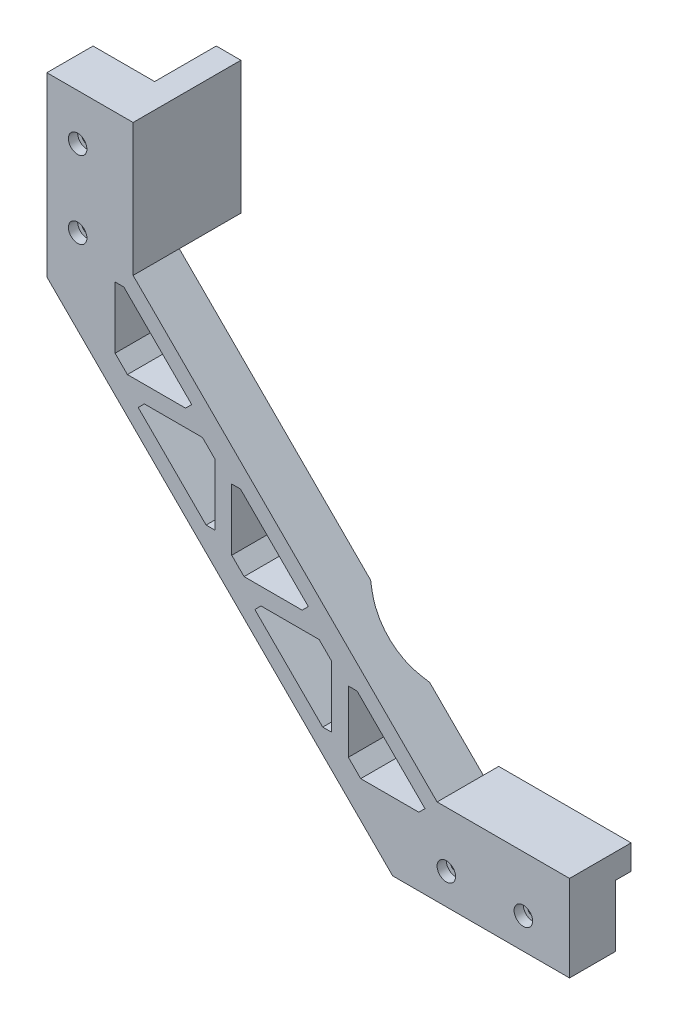
SolidWorks part; units mm, degrees
ref_plane "前视基准面" through (0, 0, 0) normal (0, 0, 1) x (1, 0, 0)
ref_plane "上视基准面" through (0, 0, 0) normal (0, 1, 0) x (1, 0, 0)
ref_plane "右视基准面" through (0, 0, 0) normal (1, 0, 0) x (0, 0, -1)
other "Configuration Table"
sketch "草图1" plane through (0, 0, 0) normal (0, 0, 1) x (1, 0, 0)
  line L0 (124.695, -160) -> (159.695, -160)
  line L1 (172.695, -180) -> (-7.695, -180) construction
  line L2 (159.695, -160) -> (159.695, -180)
  line L3 (159.695, -180) -> (102.2686, -180)
  line L4 (102.2686, -180) -> (-10, -67.7314)
  line L5 (17.8609, -53.1659) -> (-3.3523, -74.3791) construction
  line L6 (-10, -67.7314) -> (-10, -10.305)
  line L7 (-10, -10.305) -> (10, -10.305)
  line L8 (10, -10.305) -> (10, -45.305)
  line L9 (10, -45.305) -> (124.695, -160)
  line L10 (-10, 104.4) -> (-10, -160) construction
  line L11 (10, 104.4) -> (10, -160) construction
  line L12 (-14.695, -160) -> (159.695, -160) construction
  line L14 (159.695, -172.7737) -> (159.695, -167.2263) construction
  dimension "D1" = 35
  dimension "D2" = 35
  dimension "D3" = 30
extrude "凸台-拉伸1" add sketch "草图1" along normal blind 15
sketch "草图3" plane through (0, 0, 15) normal (0, 0, 1) x (1, 0, 0)
  line L0 (159.695, -160) -> (116.695, -160)
  line L2 (124.695, -160) -> (10, -45.305) construction
  line L3 (116.695, -152) -> (159.695, -152)
  line L4 (159.695, -152) -> (159.695, -160)
  line L5 (116.695, -152) -> (116.695, -160)
  dimension "D1" = 8
extrude "凸台-拉伸2" add sketch "草图3" against normal blind 35
sketch "草图4" plane through (0, 0, 15) normal (0, 0, 1) x (1, 0, 0)
  line L0 (10, -45.305) -> (10, -10.305) construction
  line L1 (10, -10.305) -> (18, -10.305)
  line L2 (10, -10.305) -> (10, -53.305)
  line L3 (10, -53.305) -> (18, -53.305)
  line L4 (18, -10.305) -> (18, -53.305)
  line L6 (10, -10.305) -> (-10, -10.305) construction
  line L7 (116.695, -152) -> (10, -45.305) construction
  dimension "D1" = 8
extrude "凸台-拉伸3" add sketch "草图4" against normal blind 35
sketch "草图5" plane through (0, 0, 15) normal (0, 0, 1) x (1, 0, 0)
  line L4 (50.0234, -93.1066) -> (50.0234, -119.9766)
  line L5 (50.0234, -119.9766) -> (76.8934, -119.9766)
  line L6 (76.8934, -119.9766) -> (50.0234, -93.1066)
  line L7 (55.5234, -125.4766) -> (82.3934, -125.4766)
  line L8 (82.3934, -125.4766) -> (82.3934, -152.3467)
  line L9 (82.3934, -152.3467) -> (55.5234, -125.4766)
  line L10 (12.1533, -55.2365) -> (12.1533, -82.1066)
  line L11 (12.1533, -82.1066) -> (39.0234, -82.1066)
  line L12 (39.0234, -82.1066) -> (12.1533, -55.2365)
  line L13 (87.8934, -130.9766) -> (87.8934, -157.8467)
  line L15 (116.695, -152) -> (18, -53.305) construction
  line L16 (17.6533, -87.6066) -> (44.5234, -87.6066)
  line L17 (44.5234, -87.6066) -> (44.5234, -114.4766)
  line L18 (44.5234, -114.4766) -> (17.6533, -87.6066)
  line L19 (-10, -67.7314) -> (102.2686, -180) construction
  line L20 (35.9264, -79.0096) -> (39.7761, -82.8593) construction
  line L21 (15.6753, -85.6286) -> (-21.6148, -48.3384) construction
  line L22 (33.1355, -76.2186) -> (37.0245, -72.3295) construction
  line L23 (19.2968, -89.2501) -> (15.4078, -93.1392) construction
  line L24 (24.3585, -82.1066) -> (24.3585, -87.6066) construction
  line L25 (87.8934, -157.8467) -> (114.7635, -157.8467)
  line L26 (114.7635, -157.8467) -> (87.8934, -130.9766)
  line L27 (44.5234, -103.4947) -> (50.0234, -103.4947) construction
  line L28 (68.5928, -119.9766) -> (68.5928, -125.4766) construction
  line L29 (82.3934, -131.3401) -> (87.8934, -131.3401) construction
  line L30 (12.1533, -76.2143) -> (12.1533, -105.29) construction
  line L31 (10, -98.1526) -> (12.1533, -98.1526) construction
  line L32 (10, 104.4) -> (10, -160) construction
  line L33 (87.8934, -157.8467) -> (71.7553, -157.8467) construction
  line L35 (74.4155, -157.8467) -> (74.4155, -160) construction
  line L36 (-14.695, -160) -> (159.695, -160) construction
  dimension "D1" = 5.5
extrude "切除-拉伸1" cut sketch "草图5" against normal through all
sketch "草图6" plane through (0, 0, 15) normal (0, 0, 1) x (1, 0, 0)
  line L0 (2.7737, 104.4) -> (-2.7737, 104.4) construction
  line L1 (173.595, -172.7737) -> (173.595, -167.2263) construction
  line L2 (159.695, -180) -> (159.695, -152) construction
  line L3 (18, -10.305) -> (-10, -10.305) construction
  circle A0 centre (0, -50.305) radius 1.6
  circle A1 centre (0, -25.305) radius 1.6
  circle A2 centre (119.695, -170) radius 1.6
  circle A3 centre (144.695, -170) radius 1.6
  point P10 (0, 104.4)
  point P13 (173.595, -170)
  dimension "D1" = 3.2
  dimension "D2" = 15
  dimension "D3" = 25
  dimension "D4" = 15
  dimension "D5" = 25
extrude "切除-拉伸2" cut sketch "草图6" against normal through all
sketch "草图7" plane through (0, 0, 15) normal (0, 0, 1) x (1, 0, 0)
  circle A0 centre (0, -25.305) radius 3
  circle A1 centre (144.695, -170) radius 1.6
  circle A2 centre (144.695, -170) radius 1.6 construction
  circle A3 centre (119.695, -170) radius 1.6
  circle A4 centre (119.695, -170) radius 1.6 construction
  circle A5 centre (0, -25.305) radius 1.6
  circle A6 centre (0, -25.305) radius 1.6 construction
  circle A7 centre (0, -50.305) radius 1.6
  circle A8 centre (0, -50.305) radius 1.6 construction
  circle A9 centre (0, -50.305) radius 3
  circle A10 centre (119.695, -170) radius 3
  circle A11 centre (144.695, -170) radius 3
  dimension "D5" = 6
  dimension "D1" = 0
  dimension "D2" = 0
  dimension "D3" = 0
  dimension "D4" = 0
extrude "切除-拉伸3" cut sketch "草图7" against normal blind 3
chamfer "倒角1" distance 4 angle 45 15 edges at (55.5234, -125.4766, 7.5) (82.3934, -125.4766, 7.5) (87.8934, -130.9766, 7.5) (76.8934, -119.9766, 7.5) (50.0234, -119.9766, 7.5) (87.8934, -157.8467, 7.5) (114.7635, -157.8467, 7.5) (82.3934, -152.3467, 7.5) (44.5234, -114.4766, 7.5) (17.6533, -87.6066, 7.5) (44.5234, -87.6066, 7.5) (39.0234, -82.1066, 7.5) (12.1533, -82.1066, 7.5) (12.1533, -55.2365, 7.5) (50.0234, -93.1066, 7.5)
sketch "草图8" plane through (159.695, 0, 0) normal (1, 0, 0) x (0, 0, -1)
  line L5 (0, -134.5866) -> (0, -115.4135)
  line L10 (16.2061, -92.5) -> (-1.1851, -117.0891)
  line L11 (-1.1851, -132.911) -> (16.2061, -157.5)
  line L12 (16.2061, -157.5) -> (25, -157.5)
  line L13 (25, -157.5) -> (25, -92.5)
  line L14 (25, -92.5) -> (16.2061, -92.5)
  line L15 (16.2061, -92.5) -> (-1.1851, -117.0891)
  line L16 (-1.1851, -132.911) -> (16.2061, -157.5)
  line L17 (16.2061, -157.5) -> (25, -157.5)
  line L18 (25, -157.5) -> (25, -92.5)
  line L19 (25, -92.5) -> (16.2061, -92.5)
  arc A2 (-1.1851, -117.0891) -> (-1.1851, -132.911) centre (10, -125) ccw
  arc A3 (-1.1851, -117.0891) -> (-1.1851, -132.911) centre (10, -125) ccw
  dimension "D1" = 2.5
extrude "切除-拉伸4" cut sketch "草图8" against normal blind 133 contours L15 A3 L16 L5
sketch "草图9" plane through (159.695, 0, 0) normal (1, 0, 0) x (0, 0, -1)
  line L1 (20, -160) -> (5, -160)
  line L2 (20, -160) -> (20, -152)
  line L3 (20, -152) -> (5, -152)
  line L4 (5, -160) -> (5, -152)
  line L5 (20, -152) -> (-15, -152) construction
  dimension "D1" = 15
extrude "切除-拉伸5" cut sketch "草图9" against normal up to surface (43 mm away) up to face at (116.695, -156, -10)
